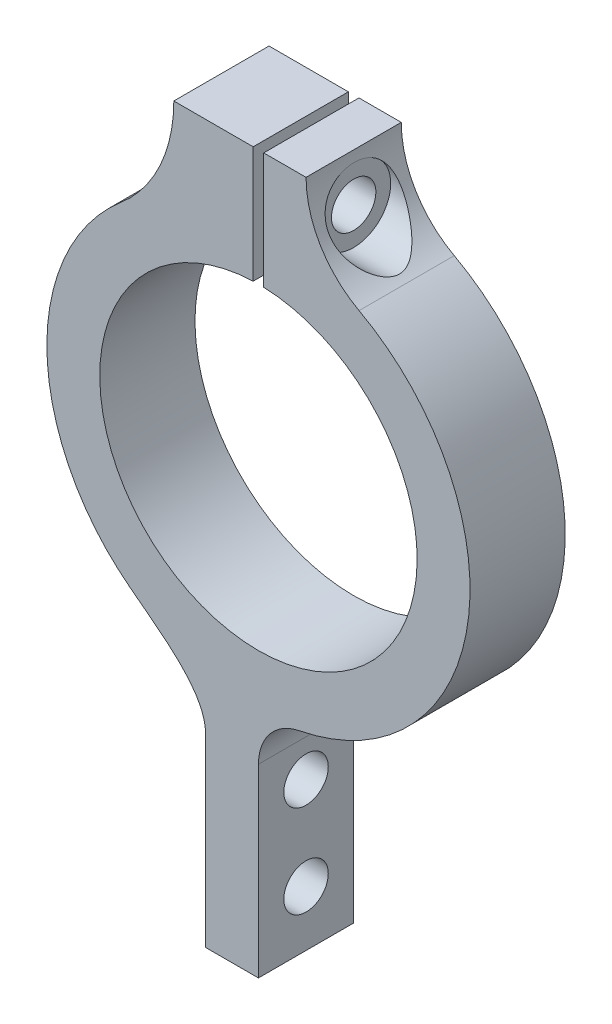
SolidWorks part; units mm, degrees
ref_plane "Front Plane" through (0, 0, 0) normal (0, 0, 1) x (1, 0, 0)
ref_plane "Top Plane" through (0, 0, 0) normal (0, 1, 0) x (1, 0, 0)
ref_plane "Right Plane" through (0, 0, 0) normal (1, 0, 0) x (0, 0, -1)
sketch "Sketch1" plane through (0, 0, 0) normal (0, 0, 1) x (1, 0, 0)
  line L0 (0, 0) -> (0, 40) construction
  line L1 (0, -48.6004) -> (0, -83.6004)
  line L2 (0, -83.6004) -> (-10, -83.6004)
  line L3 (-10, -83.6004) -> (-10, -48.6004)
  line L4 (30, 0) -> (40, 0) construction
  line L6 (0, 40) -> (0, 52) construction
  line L7 (0, 52) -> (1, 52) construction
  line L8 (1, 52) -> (1, 29.9833)
  line L9 (1, 52) -> (9, 52)
  line L11 (0, 52) -> (-1, 52) construction
  line L12 (-1, 52) -> (-1, 29.9833)
  line L13 (-1, 52) -> (-16, 52)
  arc A0 (-1, 29.9833) -> (1, 29.9833) centre (0, 0) ccw
  arc A1 (0, -48.6004) -> (7.6931, -39.2532) centre (9.525, -48.6004) cw
  arc A2 (0, 40) -> (-1, 39.9875) centre (0, 0) ccw construction
  arc A3 (9, 52) -> (19.0232, 35.1869) centre (28.1129, 52) ccw
  arc A4 (-25.9512, 30.439) -> (-26.5352, -29.9313) centre (0, 0) ccw
  circle A5 centre (0, 0) radius 40 construction
  arc A6 (-25.9512, 30.439) -> (-16, 52) centre (-44.3333, 52) ccw
  arc A8 (7.6931, -39.2532) -> (19.0232, 35.1869) centre (0, 0) ccw
  spline S0 degree 3 poles (-26.5352, -29.9313) (-20.9482, -34.8844) (-10, -40.904) (-10, -48.6004) knots 0 0 0 0 1 1 1 1
  point P27 (0, -40)
  dimension "D1" = 60
  dimension "D3" = 35
  dimension "D4" = 10
  dimension "D2" = 10
  dimension "D11" = 9.525
  dimension "D6" = 12
  dimension "D7" = 1
  dimension "D8" = 8
  dimension "D9" = 1
  dimension "D10" = 15
extrude "main body" add sketch "Sketch1" along normal blind 18
sketch "Sketch7" plane through (1, 0, 0) normal (-1, 0, 0) x (0, 0, 1)
  line L3 (9, 43) -> (9, 52) construction
  line L4 (18, 52) -> (0, 52) construction
  line L5 (9, 43) -> (0, 43) construction
  line L6 (0, 52) -> (0, 35.1869) construction
  circle A0 centre (9, 43) radius 4
  dimension "D1" = 8
sketch "Sketch12" plane through (0, 0, 0) normal (1, 0, 0) x (0, 0, -1)
  line L0 (-9, -48.6004) -> (-9, -55.6004) construction
  line L1 (-9, -62.6004) -> (-9, -73.1004) construction
  line L2 (-18, -48.6004) -> (0, -48.6004) construction
  line L3 (-9, -73.1004) -> (-9, -83.6004) construction
  line L4 (-18, -83.6004) -> (0, -83.6004) construction
  circle A0 centre (-9, -55.6004) radius 4
  circle A1 centre (-9, -55.6004) radius 7 construction
  circle A2 centre (-9, -73.1004) radius 4
  circle A3 centre (-9, -73.1004) radius 7 construction
  dimension "D1" = 8
  dimension "D2" = 14
  dimension "D3" = 14
  dimension "D4" = 8
hole_wizard "M8 Clearance Hole1" positions "Sketch13" profile "Sketch14" hole size "M8" standard "ANSI Metric" end condition through all
sketch "Sketch13" plane through (1, 0, 0) normal (-1, 0, 0) x (0, 0, 1)
  point P0 (9, 43)
sketch "Sketch14" plane through (1, 43, 9) normal (0, 1, 0) x (0, 0, 1)
  line L0 (0, 0) -> (0, 39)
  line L1 (0, 39) -> (4.2, 39)
  line L2 (4.2, 39) -> (4.2, 0)
  line L5 (4.2, 0) -> (0, 0)
  line L11 (0, -6.35) -> (0, 107.95) construction
  dimension "Thru Hole Dia." = 8.4
  dimension "Thru Hole Depth" = 39
hole_wizard "M8 Clearance Hole2" positions "Sketch15" profile "Sketch16" hole size "M8" standard "ANSI Metric" end condition through all
sketch "Sketch15" plane through (1, 0, 0) normal (-1, 0, 0) x (0, 0, 1)
  point P0 (9, 43)
sketch "Sketch16" plane through (1, 43, 9) normal (0, 1, 0) x (0, 0, -1)
  line L0 (0, 0) -> (0, 41)
  line L1 (0, 41) -> (4.2, 41)
  line L2 (4.2, 41) -> (4.2, 0)
  line L5 (4.2, 0) -> (0, 0)
  line L11 (0, -6.35) -> (0, 107.95) construction
  dimension "Thru Hole Dia." = 8.4
  dimension "Thru Hole Depth" = 41
sketch "Sketch17" plane through (0, 0, 18) normal (0, 0, 1) x (1, 0, 0)
  line L0 (-16, 52) -> (-16, 25.3772)
  line L1 (9, 52) -> (9, 28.6182)
  arc A0 (-1, 29.9833) -> (1, 29.9833) centre (0, 0) ccw construction
hole_wizard "M8 Clearance Hole3" positions "Sketch18" profile "Sketch19" hole size "M8" standard "ANSI Metric" end condition through all
sketch "Sketch18" plane through (0, 0, 0) normal (1, 0, 0) x (0, 0, -1)
  point P0 (-9, -55.6004)
  point P3 (-9, -73.1004)
sketch "Sketch19" plane through (0, -55.6004, 9) normal (0, 1, 0) x (0, 0, -1)
  line L0 (0, 0) -> (0, 40)
  line L1 (0, 40) -> (4.2, 40)
  line L2 (4.2, 40) -> (4.2, 0)
  line L5 (4.2, 0) -> (0, 0)
  line L11 (0, -6.35) -> (0, 107.95) construction
  dimension "Thru Hole Dia." = 8.4
  dimension "Thru Hole Depth" = 40
ref_plane "Plane1" through (-16, 0, 0) normal (-1, 0, 0) x (0, 0, 1)
sketch "Sketch26" plane through (-16, 0, 0) normal (-1, 0, 0) x (0, 0, 1)
  circle A0 centre (9, 43) radius 7
  dimension "D1" = 14
ref_plane "Plane2" through (9, 0, 0) normal (1, 0, 0) x (0, 0, -1)
sketch "Sketch27" plane through (9, 0, 0) normal (1, 0, 0) x (0, 0, -1)
  circle A0 centre (-9, 43) radius 7
  circle A1 centre (-9, 43) radius 7 construction
extrude "Cut-Extrude2" cut sketch "Sketch27" along normal through all
sketch "Sketch29" plane through (0, 0, 18) normal (0, 0, 1) x (1, 0, 0)
  line L0 (-16, 52) -> (-42.54, 52) construction
  line L1 (-42.54, 52) -> (-42.54, 0) construction
  line L2 (-42.54, 0) -> (-40, 0) construction
  arc A0 (-25.9512, 30.439) -> (-26.5352, -29.9313) centre (0, 0) ccw construction
  dimension "D1" = 2.54
